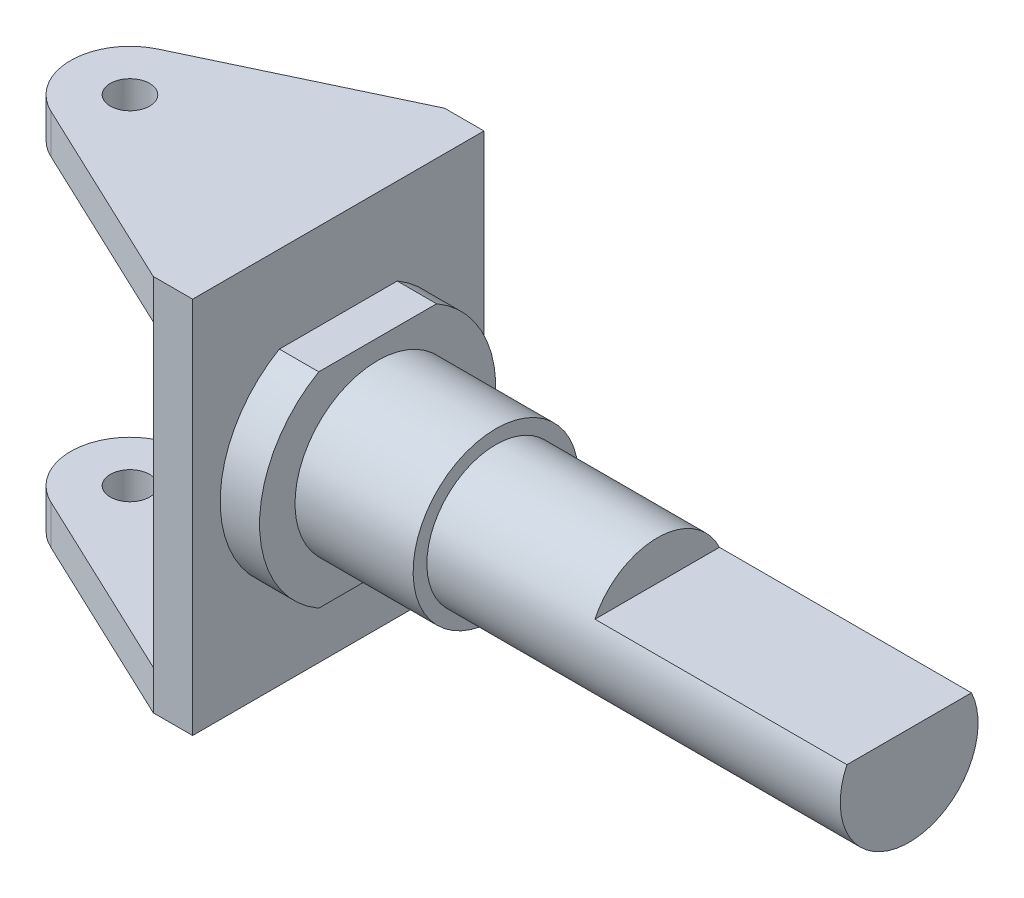
SolidWorks part; units mm, degrees
ref_plane "Front Plane" through (0, 0, 0) normal (0, 0, 1) x (1, 0, 0)
ref_plane "Top Plane" through (0, 0, 0) normal (0, 1, 0) x (1, 0, 0)
ref_plane "Right Plane" through (0, 0, 0) normal (1, 0, 0) x (0, 0, -1)
sketch "Sketch1" plane through (0, 0, 0) normal (0, 0, 1) x (1, 0, 0)
  line L0 (-58, -38) -> (0, -38)
  line L1 (0, -38) -> (0, 38)
  line L2 (0, 38) -> (-58, 38)
  dimension "D1" = 76
  dimension "D2" = 58
extrude "Extrude-Thin1" add sketch "Sketch1" along normal mid plane 74 thin thin type one direction wall 10
sketch "Sketch2" plane through (0, 48, 0) normal (0, 1, 0) x (1, 0, 0)
  line L0 (10, 37) -> (0, 37)
  line L1 (10, 37) -> (-58, 37) construction
  line L2 (0, 37) -> (-49.3703, 13.6322)
  line L3 (-49.3703, -13.6322) -> (0, -37)
  line L4 (10, -37) -> (-58, -37) construction
  line L5 (0, -37) -> (10, -37)
  line L6 (-58, -37) -> (-58, 37) construction
  line L7 (0, 0) -> (-76.0181, 0) construction
  arc A0 (-49.3703, 13.6322) -> (-49.3703, -13.6322) centre (-42.9179, 0) ccw
  circle A1 centre (-42.9179, 0) radius 5
  line M6 (10, 37) -> (-58, 37)
  line M7 (-58, 37) -> (-58, -37)
  line M8 (-58, -37) -> (10, -37)
  dimension "D3" = 10
  dimension "D1" = 10
  dimension "D2" = 10
extrude "Cut-Extrude1" cut sketch "Sketch2" against normal through all and the other way through all contours A0 L2 M6 M7 | A0 L3 M7 M8 region at (-39.0036, 48, 27.4747) region at (-39.0036, 48, -27.4747)
extrude "Cut-Extrude2" cut sketch "Sketch2<3>" against normal through all contours L7 A1 | A1 L7 region at (-42.9179, 48, 2.1221) region at (-42.9179, 48, -2.1221)
sketch "Sketch2<3>" plane through (0, 48, 0) normal (0, 1, 0) x (1, 0, 0) same geometry as "Sketch2"
sketch "Sketch3" plane through (10, 0, 0) normal (1, 0, 0) x (0, 0, -1)
  line L0 (-14.9666, 26) -> (14.9666, 26)
  line L1 (-14.9666, -26) -> (14.9666, -26)
  arc A0 (-14.9666, 26) -> (-14.9666, -26) centre (0, 0) ccw
  arc A1 (14.9666, -26) -> (14.9666, 26) centre (0, 0) ccw
  dimension "D1" = 60
  dimension "D2" = 52
extrude "Boss-Extrude1" add sketch "Sketch3" along normal blind 10
sketch "Sketch4" plane through (20, 0, 0) normal (1, 0, 0) x (0, 0, -1)
  circle A0 centre (0, 0) radius 21
  dimension "D1" = 42
extrude "Boss-Extrude2" add sketch "Sketch4" along normal blind 30
sketch "Sketch5" plane through (50, 0, 0) normal (1, 0, 0) x (0, 0, -1)
  circle A0 centre (0, 0) radius 17.5
  dimension "D1" = 35
extrude "Boss-Extrude3" add sketch "Sketch5" along normal blind 105
sketch "Sketch6" plane through (155, 0, 0) normal (1, 0, 0) x (0, 0, -1)
  line L0 (-15.8114, 7.5) -> (15.8114, 7.5)
  circle A0 centre (0, 0) radius 17.5 construction
  arc A1 (15.8114, 7.5) -> (-15.8114, 7.5) centre (0, 0) ccw
  dimension "D1" = 7.5
extrude "Cut-Extrude3" cut sketch "Sketch6" against normal blind 64
